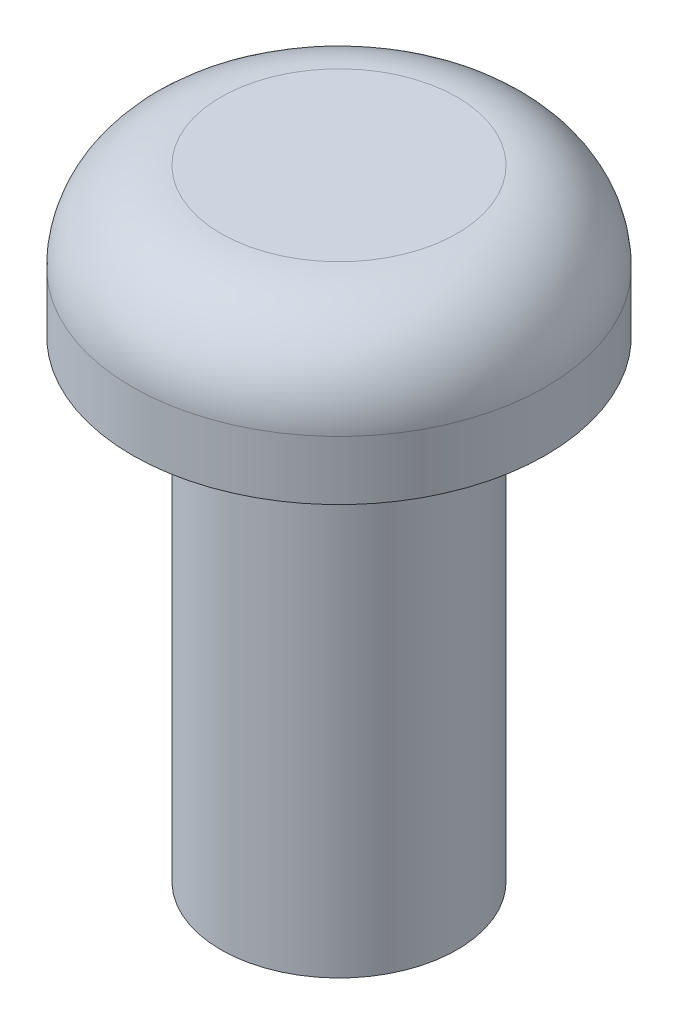
SolidWorks part; units mm, degrees
ref_plane "Front Plane" through (0, 0, 0) normal (0, 0, 1) x (1, 0, 0)
ref_plane "Top Plane" through (0, 0, 0) normal (0, 1, 0) x (1, 0, 0)
ref_plane "Right Plane" through (0, 0, 0) normal (1, 0, 0) x (0, 0, -1)
sketch "Sketch1" plane through (0, 0, 0) normal (0, 0, 1) x (1, 0, 0)
  line L0 (2, 0) -> (3.5, 0)
  line L1 (3.5, 0) -> (3.5, 1)
  line L2 (2, 2.5) -> (0, 2.5)
  line L3 (2, 0) -> (2, -8)
  line L4 (2, -8) -> (0, -8)
  line L5 (0, -8) -> (0, 2.5)
  arc A0 (3.5, 1) -> (2, 2.5) centre (2, 1) ccw
  dimension "D1" = 2
  dimension "D2" = 8
  dimension "D3" = 3.5
  dimension "D4" = 2.5
revolve "Revolve1" add sketch "Sketch1" angle 360 about L5
